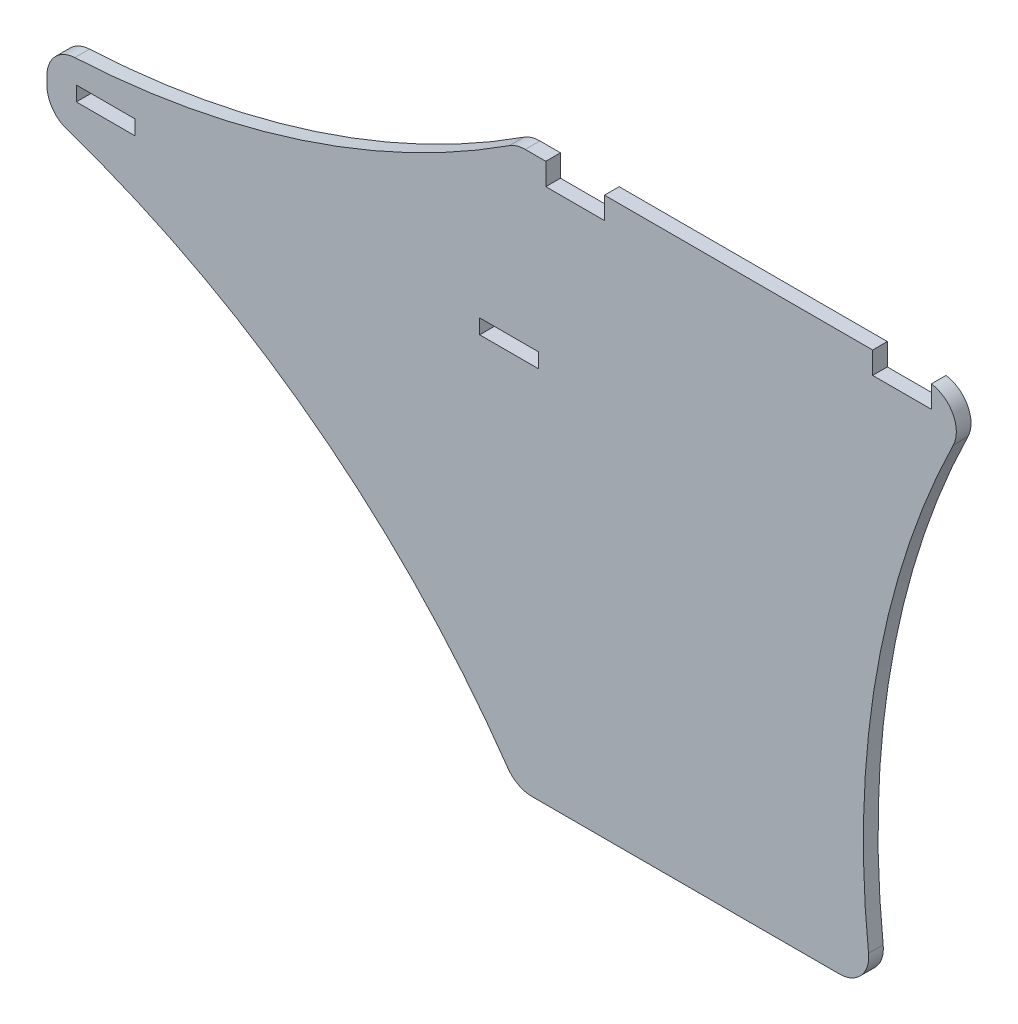
SolidWorks part; units mm, degrees
ref_plane "Front Plane" through (0, 0, 0) normal (0, 0, 1) x (1, 0, 0)
ref_plane "Top Plane" through (0, 0, 0) normal (0, 1, 0) x (1, 0, 0)
ref_plane "Right Plane" through (0, 0, 0) normal (1, 0, 0) x (0, 0, -1)
sketch "Sketch1" plane through (0, 0, 0) normal (0, 0, 1) x (1, 0, 0)
  line L0 (-119.0625, -9.525) -> (-119.0625, 15.875)
  line L1 (96.8854, 79.375) -> (84.1854, 79.375)
  line L2 (96.8854, 79.375) -> (96.8854, 69.85)
  line L3 (96.8854, 69.85) -> (122.2854, 69.85)
  line L4 (122.2854, 69.85) -> (122.2854, 79.375)
  line L5 (122.2854, 79.375) -> (238.3946, 79.375)
  line L6 (238.3946, 79.375) -> (238.3946, 69.85)
  line L7 (238.3946, 69.85) -> (263.7946, 69.85)
  line L8 (263.7946, 69.85) -> (263.7946, 79.375)
  line L9 (263.7946, 79.375) -> (282.8446, 79.375)
  line L11 (238.3946, -161.798) -> (84.1854, -161.798)
  line L12 (96.8854, 76.2) -> (96.8854, 69.85) construction
  line L14 (122.2854, 69.85) -> (122.2854, 76.2) construction
  line L15 (96.8854, 69.85) -> (122.2854, 69.85) construction
  line L16 (238.3946, 69.85) -> (238.3946, 76.2) construction
  line L17 (238.3946, 69.85) -> (263.7946, 69.85) construction
  line L18 (263.7946, 76.2) -> (263.7946, 69.85) construction
  line L19 (238.3946, 76.2) -> (263.7946, 76.2) construction
  line L20 (140.462, -161.798) -> (220.218, -161.798) construction
  line L21 (-106.3625, 6.35) -> (-106.3625, 0) construction
  line L22 (-119.0625, 3.175) -> (-106.3625, 3.175) construction
  arc A0 (-119.0625, -9.525) -> (84.1854, -161.798) centre (-232.8212, -373.1456) cw
  arc A1 (-119.0625, 15.875) -> (84.1854, 79.375) centre (-126.5306, 396.8018) ccw
  arc A2 (282.8446, 79.375) -> (238.3946, -161.798) centre (615.3743, -106.5955) ccw
  dimension "D6" = 381
  dimension "D1" = 3.175
  dimension "D2" = 19.05
  dimension "D3" = 12.7
  dimension "D4" = 12.7
  dimension "D5" = 25.4
extrude "Extrude1" add sketch "Sketch1" along normal blind 6.35
sketch "Sketch2" plane through (0, 0, 6.35) normal (0, 0, 1) x (1, 0, 0)
  line L1 (68.2625, 6.35) -> (93.6625, 6.35)
  line L2 (68.2625, 6.35) -> (68.2625, 0)
  line L3 (68.2625, 0) -> (93.6625, 0)
  line L4 (93.6625, 6.35) -> (93.6625, 0)
  line L5 (-106.3625, 6.35) -> (-80.9625, 6.35)
  line L6 (-106.3625, 6.35) -> (-106.3625, 0)
  line L7 (-106.3625, 0) -> (-80.9625, 0)
  line L8 (-80.9625, 6.35) -> (-80.9625, 0)
extrude "Cut-Extrude1" cut sketch "Sketch2" against normal up to next
fillet "Fillet1" radius 12.7 6 edges at (84.1854, -161.798, 3.175) (238.3946, -161.798, 3.175) (282.8446, 79.375, 3.175) (84.1854, 79.375, 3.175) (-119.0625, -9.525, 3.175) (-119.0625, 15.875, 3.175)
